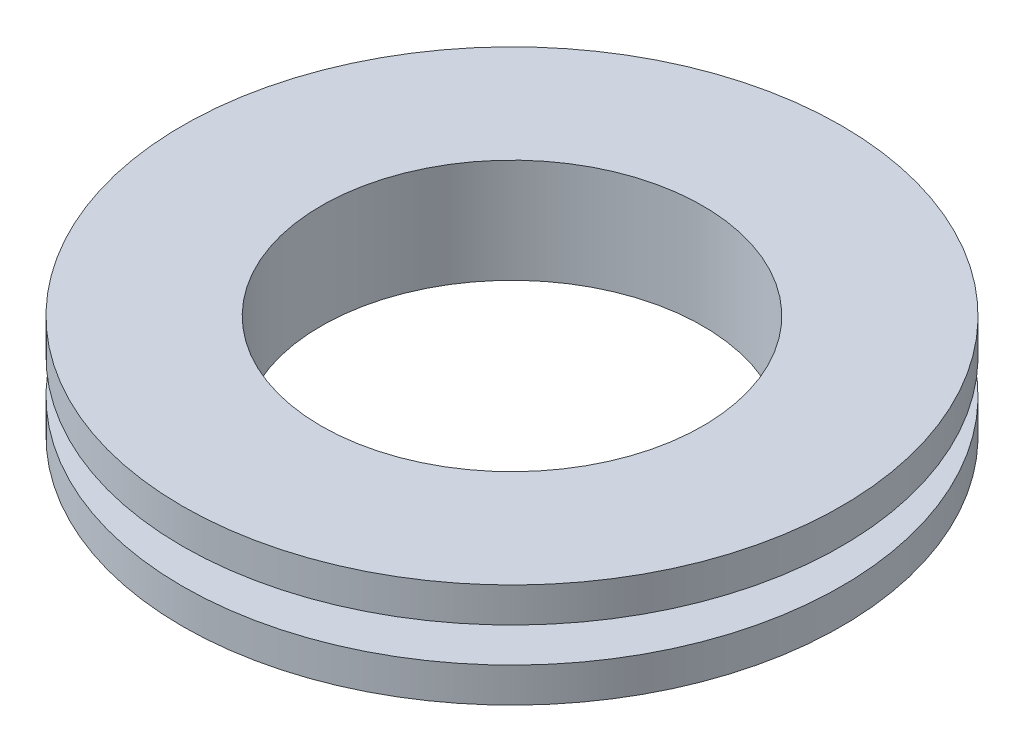
SolidWorks part; units mm, degrees
ref_plane "Front Plane" through (0, 0, 0) normal (0, 0, 1) x (1, 0, 0)
ref_plane "Top Plane" through (0, 0, 0) normal (0, 1, 0) x (1, 0, 0)
ref_plane "Right Plane" through (0, 0, 0) normal (1, 0, 0) x (0, 0, -1)
sketch "Sketch1" plane through (0, 0, 0) normal (0, 1, 0) x (1, 0, 0)
  circle A0 centre (0, 0) radius 5.5
  circle A1 centre (0, 0) radius 7.5
  dimension "D1" = 11
  dimension "D2" = 15
extrude "Boss-Extrude1" add sketch "Sketch1" along normal blind 3
sketch "Sketch2" plane through (0, 3, 0) normal (0, 1, 0) x (1, 0, 0)
  circle A0 centre (0, 0) radius 9.5
  circle A1 centre (0, 0) radius 7.5
  dimension "D1" = 15
  dimension "D2" = 19
extrude "Boss-Extrude2" add sketch "Sketch2" against normal blind 1
sketch "Sketch3" plane through (0, 0, 0) normal (0, -1, 0) x (1, 0, 0)
  circle A0 centre (0, 0) radius 7.5
  circle A1 centre (0, 0) radius 9.5
  dimension "D1" = 19
  dimension "D2" = 15
extrude "Boss-Extrude3" add sketch "Sketch3" against normal blind 1
fillet "Fillet1" radius 0.5 2 edges at (0, 2, 7.5) (0, 1, -7.5)
